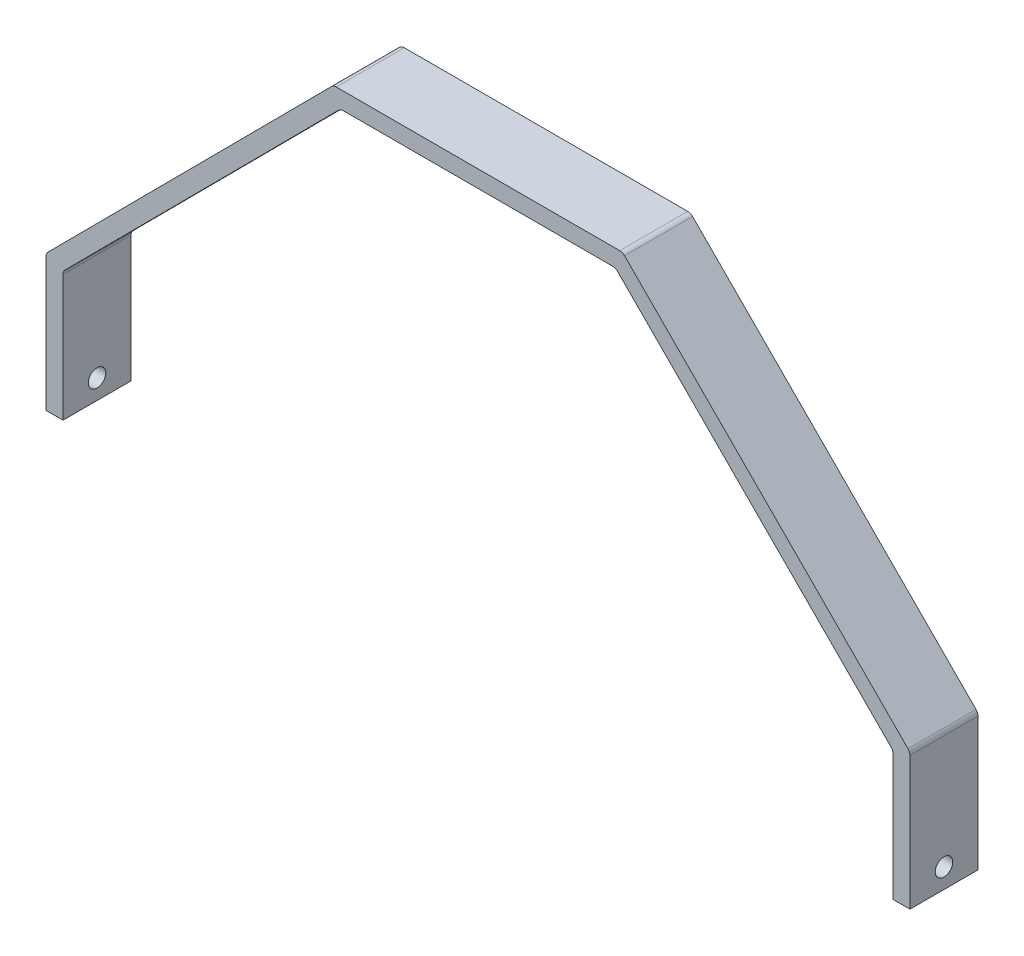
SolidWorks part; units mm, degrees
material "Thornel VCB-20 Carbon Cloth"
ref_plane "Front Plane" through (0, 0, 0) normal (0, 0, 1) x (1, 0, 0)
ref_plane "Top Plane" through (0, 0, 0) normal (0, 1, 0) x (1, 0, 0)
ref_plane "Right Plane" through (0, 0, 0) normal (1, 0, 0) x (0, 0, -1)
sketch "Sketch1" plane through (0, 0, 0) normal (0, 0, 1) x (1, 0, 0)
  line L0 (42.5, 0) -> (-42.5, 0)
  line L1 (42.5, 0) -> (127, -85)
  line L2 (127, -85) -> (127, -125)
  line L3 (-42.5, 0) -> (-127, -85)
  line L4 (-127, -85) -> (-127, -125)
  line L5 (122, -87.0624) -> (122, -125)
  line L6 (40.4203, -5) -> (122, -87.0624)
  line L7 (40.4203, -5) -> (-40.4203, -5)
  line L8 (-40.4203, -5) -> (-122, -87.0624)
  line L9 (-122, -87.0624) -> (-122, -125)
  line L10 (-127, -125) -> (-122, -125)
  line L11 (122, -125) -> (127, -125)
  point P4 (0, 0)
  dimension "D1" = 85
  dimension "D2" = 254
  dimension "D3" = 125
  dimension "D4" = 127
  dimension "D5" = 40
  dimension "D6" = 5
extrude "Boss-Extrude1" add sketch "Sketch1" along normal blind 20
fillet "Fillet1" radius 2 8 edges at (122, -87.0624, 10) (40.4203, -5, 10) (-40.4203, -5, 10) (-122, -87.0624, 10) (-127, -85, 10) (127, -85, 10) (-42.5, 0, 10) (42.5, 0, 10)
sketch "Sketch2" plane through (-127, 0, 0) normal (-1, 0, 0) x (0, 0, 1)
  line L0 (0, -125) -> (10, -125) construction
  line L1 (20, -125) -> (0, -125) construction
  line L2 (10, -125) -> (10, -85.825) construction
  line L3 (20, -85.825) -> (0, -85.825) construction
  line L4 (0, -105.4125) -> (20, -105.4125) construction
  line L5 (0, -85.825) -> (0, -125) construction
  line L6 (20, -85.825) -> (20, -125) construction
  circle A0 centre (10, -105.4125) radius 2.5
  circle A1 centre (10, -119.231) radius 2.5748
  dimension "D1" = 5
extrude "Cut-Extrude1" cut sketch "Sketch2" against normal through all contours A1 region at (-127, -119.231, 10)
